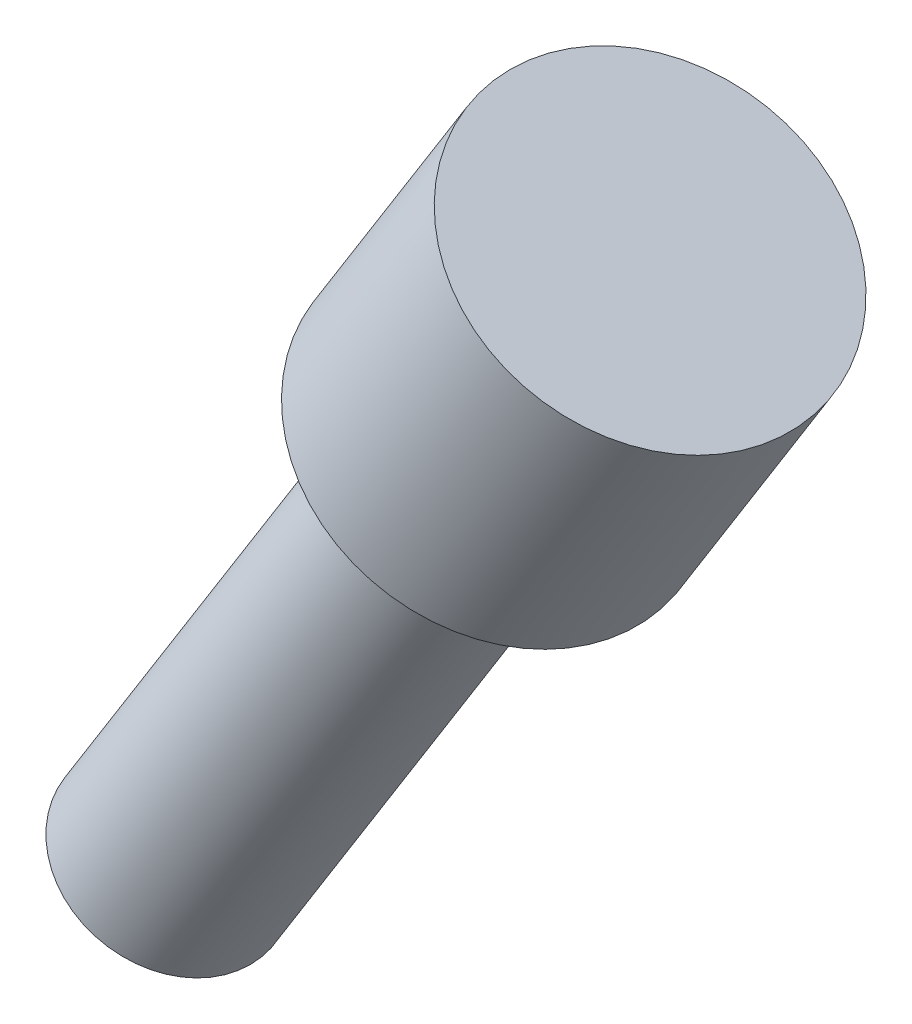
SolidWorks part; units mm, degrees
ref_plane "Plan de face" through (0, 0, 0) normal (0, 0, 1) x (1, 0, 0)
ref_plane "Plan de dessus" through (0, 0, 0) normal (0, 1, 0) x (1, 0, 0)
ref_plane "Plan de droite" through (0, 0, 0) normal (1, 0, 0) x (0, 0, -1)
sketch "Esquisse1" plane through (0.8076, 1.2922, 0) normal (-0.53, -0.848, 0) x (0.848, -0.53, 0)
  circle A0 centre (-28.8193, -165) radius 2.3
  circle A2 centre (-28.8193, -165) radius 2.3 construction
  point P2 (-28.8193, -165)
extrude "Boss.-Extru.1" add sketch "Esquisse1" against normal up to surface (15 mm away)
sketch "Esquisse2" plane through (8.7576, 14.0122, 0) normal (0.53, 0.848, 0) x (0.848, -0.53, 0)
  circle A0 centre (-28.8193, 165) radius 4
  circle A2 centre (-28.8193, 165) radius 4 construction
extrude "Boss.-Extru.2" add sketch "Esquisse2" along normal blind 7
